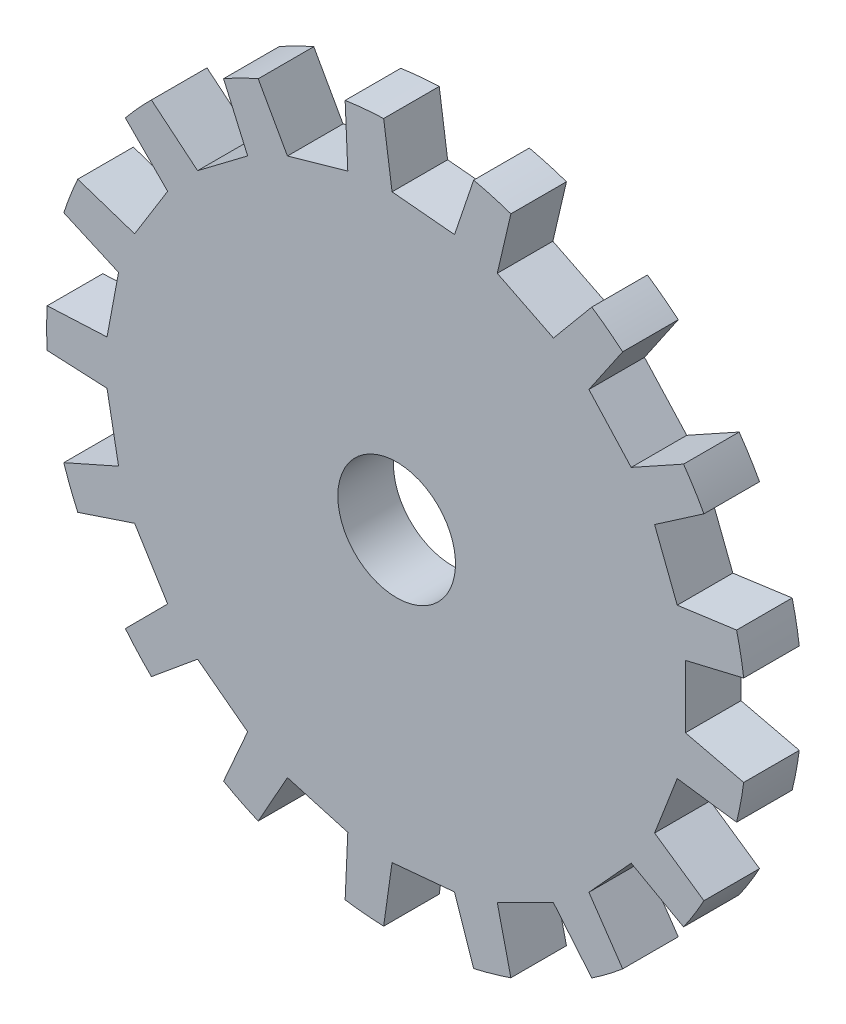
SolidWorks part; units mm, degrees
material "Plain Carbon Steel"
ref_plane "Front Plane" through (0, 0, 0) normal (0, 0, 1) x (1, 0, 0)
ref_plane "Top Plane" through (0, 0, 0) normal (0, 1, 0) x (1, 0, 0)
ref_plane "Right Plane" through (0, 0, 0) normal (1, 0, 0) x (0, 0, -1)
sketch "Sketch1" plane through (0, 0, 0) normal (0, 0, 1) x (1, 0, 0)
  circle A0 centre (0, 0) radius 28.3346
  dimension "D1" = 56.6692
extrude "Boss-Extrude1" add sketch "Sketch1" along normal blind 4.5
sketch "Sketch2" plane through (0, 0, 0) normal (0, 0, 1) x (1, 0, 0)
  line L0 (23.3784, -2.54) -> (29.5346, -4)
  line L1 (29.5346, -4) -> (29.5346, 4)
  line L2 (29.5346, 4) -> (23.3784, 2.54)
  line L3 (23.3784, 2.54) -> (23.3784, -2.54)
  dimension "D1" = 23.3784
  dimension "D2" = 2.54
  dimension "D3" = 6.1562
  dimension "D4" = 1.46
  dimension "D5" = 8
  dimension "D6" = 5.08
extrude "Cut-Extrude2" cut sketch "Sketch2" against normal blind 5.5 and the other way blind 5.5
ref_axis "Axis1" through (0, 0, -0.225) along (0, 0, 1)
pattern_circular "CirPattern1" count 17 over 360 about axis through (0, 0, -0.225) along (0, 0, 1) of "Cut-Extrude2"
sketch "Sketch3" plane through (0, 0, 0) normal (0, 0, 1) x (1, 0, 0)
  circle A0 centre (0, 0) radius 4.7625
  dimension "D1" = 9.525
extrude "Cut-Extrude4" cut sketch "Sketch3" against normal blind 6.5 and the other way blind 6.5
